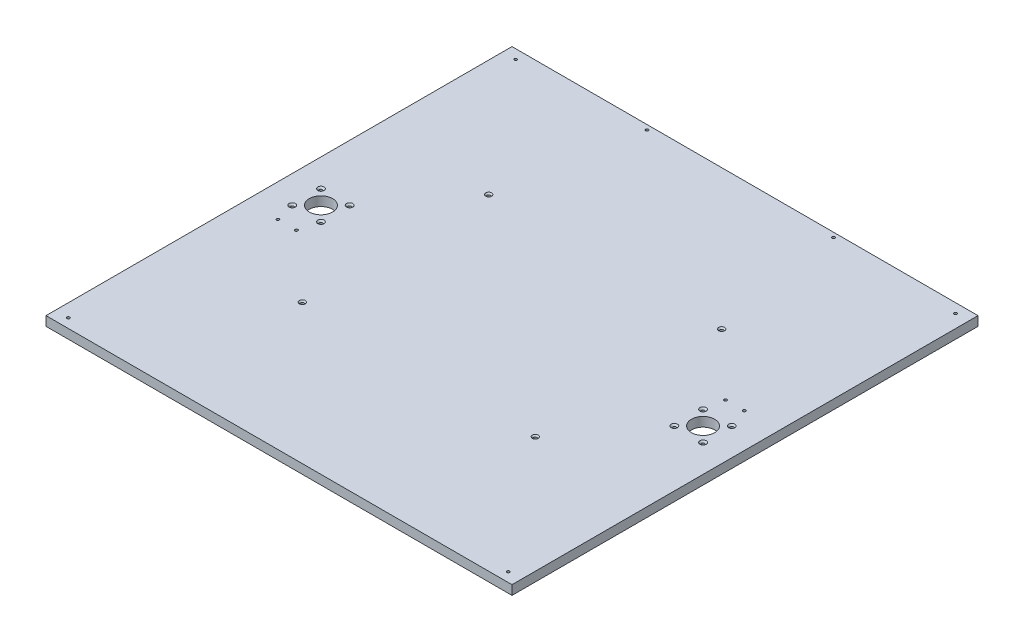
SolidWorks part; units mm, degrees
material "Buk"
ref_plane "Płaszczyzna przednia" through (0, 0, 0) normal (0, 0, 1) x (1, 0, 0)
ref_plane "Płaszczyzna górna" through (0, 0, 0) normal (0, 1, 0) x (1, 0, 0)
ref_plane "Płaszczyzna prawa" through (0, 0, 0) normal (1, 0, 0) x (0, 0, -1)
sketch "Szkic1" plane through (0, 0, 0) normal (0, 1, 0) x (1, 0, 0)
  line L1 (0, 0) -> (500, 0)
  line L2 (0, 0) -> (0, 500)
  line L3 (0, 500) -> (500, 500)
  line L4 (500, 0) -> (500, 500)
  dimension "D1" = 500
  dimension "D2" = 500
extrude "Dodanie-wyciągnięcie1" add sketch "Szkic1" along normal blind 10
sketch "Szkic2" plane through (0, 10, 0) normal (0, 1, 0) x (1, 0, 0)
  line L0 (0, 500) -> (0, 0) construction
  line L1 (500, 500) -> (0, 500) construction
  line L3 (500, 0) -> (500, 500) construction
  circle A0 centre (45, 250) radius 12.5
  circle A1 centre (455, 250) radius 12.5
  dimension "D1" = 25
  dimension "D2" = 45
  dimension "D3" = 250
  dimension "D4" = 25
  dimension "D5" = 45
extrude "Wytnij-wyciągnięcie1" cut sketch "Szkic2" against normal through all
sketch "Szkic5" plane through (0, 10, 0) normal (0, 1, 0) x (1, 0, 0)
  line L0 (0, 500) -> (0, 0) construction
  line L1 (0, 0) -> (500, 0) construction
  circle A0 centre (125, 150) radius 1.6
  circle A1 centre (375, 150) radius 1.6
  circle A2 centre (375, 350) radius 1.6
  circle A3 centre (125, 350) radius 1.6
  dimension "D1" = 3.2
  dimension "D2" = 125
  dimension "D3" = 150
  dimension "D4" = 2
  dimension "D5" = 2
hole_wizard "Pogłębienie stożkowe pod M3 Wkręt ustalający1" positions "Szkic6" profile "Szkic7" countersink size "M3" standard "Ansi Metric" end condition through all
sketch "Szkic6" plane through (0, 10, 0) normal (0, 1, 0) x (1, 0, 0)
  point P0 (439.6, 265.4)
  point P3 (439.6, 234.6)
  point P6 (470.4, 234.6)
  point P9 (470.4, 265.4)
  point P12 (60.4, 234.6)
  point P15 (60.4, 265.4)
  point P18 (29.6, 234.6)
  point P21 (29.6, 265.4)
sketch "Szkic7" plane through (439.6, 10, -265.4) normal (1, 0, 0) x (0, 0, 1)
  line L0 (0, 0) -> (0, 10)
  line L1 (0, 10) -> (1.7, 10)
  line L2 (1.7, 10) -> (1.7, 1.66)
  line L3 (1.7, 1.66) -> (3.36, 0)
  line L5 (3.36, 0) -> (0, 0)
  line L6 (-1.7, 1.66) -> (-3.36, 0) construction
  line L11 (0, -6.35) -> (0, 107.95) construction
  dimension "Œrednica otworu na wylot" = 3.4
  dimension "G³êbokoœæ otworu na wylot" = 10
  dimension "Œrednica zewnêtrznego pog³êbienia sto¿kowego" = 6.72
  dimension "K¹t zewnêtrznego pog³êbienia sto¿kowego" = 90
hole_wizard "Pogłębienie stożkowe pod M3 wkręt do części metalowych z łbem soczewkowym1" positions "Szkic8" profile "Szkic9" countersink size "M3" standard "Ansi Metric"
sketch "Szkic8" plane through (0, 10, 0) normal (0, 1, 0) x (1, 0, 0)
  point P0 (375, 350)
  point P3 (375, 150)
  point P6 (125, 350)
  point P9 (125, 150)
sketch "Szkic9" plane through (375, 10, -350) normal (1, 0, 0) x (0, 0, 1)
  line L0 (0, 0) -> (0, 11.0215)
  line L1 (0, 11.0215) -> (1.7, 10)
  line L2 (1.7, 10) -> (1.7, 1.45)
  line L3 (1.7, 1.45) -> (3.15, 0)
  line L5 (3.15, 0) -> (0, 0)
  line L6 (-1.7, 1.45) -> (-3.15, 0) construction
  line L10 (0, 11.0215) -> (-1.7, 10) construction
  line L11 (0, -6.35) -> (0, 107.95) construction
  dimension "Œrednica otworu" = 3.4
  dimension "G³êbokoœc otworu" = 10
  dimension "Œrednica zewnêtrznego pog³êbienia sto¿kowego" = 6.3
  dimension "K¹t zewnêtrznego pog³êbienia sto¿kowego" = 90
  dimension "K¹t wiert³a" = 118
hole_wizard "Otwory ustalające Ø3.0mm1" positions "Szkic10" profile "Szkic11" hole size "Ø3.0" standard "Ansi Metric"
sketch "Szkic10" plane through (0, 0, 0) normal (0, -1, 0) x (-1, 0, 0)
  line L0 (-10, 0) -> (-10, 500) construction
  line L2 (-500, 500) -> (0, 500) construction
  line L3 (-490, 500) -> (-490, 0) construction
  line L4 (0, 0) -> (-500, 0) construction
  point P0 (-486, 490)
  point P2 (-486, 10)
  point P4 (-14, 10)
  point P6 (-14, 490)
  dimension "D1" = 4
  dimension "D2" = 10
  dimension "D3" = 4
  dimension "D4" = 10
  dimension "D5" = 4
  dimension "D6" = 10
  dimension "D7" = 4
  dimension "D8" = 10
sketch "Szkic11" plane through (486, 0, -490) normal (1, 0, 0) x (0, 0, -1)
  line L0 (0, 0) -> (0, 10.9013)
  line L1 (0, 10.9013) -> (1.5, 10)
  line L2 (1.5, 10) -> (1.5, 0)
  line L5 (1.5, 0) -> (0, 0)
  line L10 (0, 10.9013) -> (-1.5, 10) construction
  line L11 (0, -6.35) -> (0, 107.95) construction
  dimension "Œrednica otworu" = 3
  dimension "G³êbokoœæ otworu" = 10
  dimension "K¹t wiert³a" = 118
hole_wizard "Otwory ustalające Ø3.0mm2" positions "Szkic12" profile "Szkic13" hole size "Ø3.0" standard "Ansi Metric"
sketch "Szkic12" plane through (0, 0, 0) normal (0, -1, 0) x (-1, 0, 0)
  line L0 (-500, 500) -> (0, 500) construction
  line L1 (0, 500) -> (0, 0) construction
  line L2 (-500, 0) -> (-500, 500) construction
  point P0 (-150, 495)
  point P2 (-350, 495)
  dimension "D1" = 5
  dimension "D2" = 150
  dimension "D3" = 5
  dimension "D4" = 150
sketch "Szkic13" plane through (150, 0, -495) normal (1, 0, 0) x (0, 0, -1)
  line L0 (0, 0) -> (0, 10.9013)
  line L1 (0, 10.9013) -> (1.5, 10)
  line L2 (1.5, 10) -> (1.5, 0)
  line L5 (1.5, 0) -> (0, 0)
  line L10 (0, 10.9013) -> (-1.5, 10) construction
  line L11 (0, -6.35) -> (0, 107.95) construction
  dimension "Œrednica otworu" = 3
  dimension "G³êbokoœæ otworu" = 10
  dimension "K¹t wiert³a" = 118
hole_wizard "Ø3.0mm Dowel Hole1" positions "Sketch3" profile "Sketch2" hole size "Ø3.0" standard "ANSI Metric" end condition through all
sketch "Sketch3" plane through (0, 10, 0) normal (0, 1, 0) x (1, 0, 0)
  point P0 (442.9854, 286.253)
  point P3 (462.9854, 286.253)
  point P6 (55, 213.747)
  point P9 (35, 213.747)
sketch "Sketch2" plane through (442.9854, 10, -286.253) normal (1, 0, 0) x (0, 0, 1)
  line L0 (0, 0) -> (0, 10)
  line L1 (0, 10) -> (1.5, 10)
  line L2 (1.5, 10) -> (1.5, 0)
  line L5 (1.5, 0) -> (0, 0)
  line L11 (0, -6.35) -> (0, 107.95) construction
  dimension "Thru Hole Dia." = 3
  dimension "Thru Hole Depth" = 10
